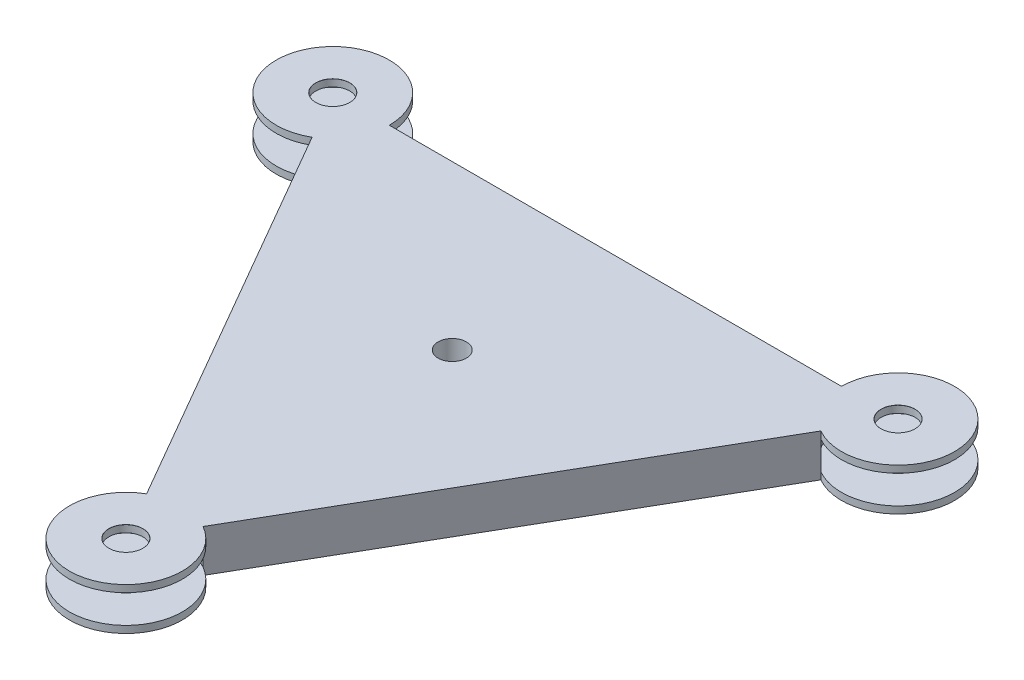
SolidWorks part; units mm, degrees
ref_plane "Plan de face" through (0, 0, 0) normal (0, 0, 1) x (1, 0, 0)
ref_plane "Plan de dessus" through (0, 0, 0) normal (0, 1, 0) x (1, 0, 0)
ref_plane "Plan de droite" through (0, 0, 0) normal (1, 0, 0) x (0, 0, -1)
sketch "Esquisse1" plane through (0, 0, 0) normal (0, 1, 0) x (1, 0, 0)
  line L3 (50, -28.8675) -> (-100, 57.735) construction
  line L6 (-50, -28.8675) -> (100, 57.735) construction
  line L16 (100, 57.735) -> (0, -115.4701)
  line L17 (0, -115.4701) -> (-100, 57.735)
  line L19 (-100, 57.735) -> (100, 57.735)
  circle A6 centre (0, 0) radius 5
  circle A7 centre (100, 57.735) radius 20
  circle A9 centre (0, -115.4701) radius 20
  circle A10 centre (-100, 57.735) radius 20
  point P11 (0, 0)
  point P12 (5.3523, 54.348)
  point P36 (0, 50)
  point P38 (0, 50)
  point P40 (0, 50)
  point P41 (0, 50)
  dimension "D2" = 5.3523
  dimension "D3" = 200
  dimension "D5" = 40
  dimension "D1" = 200
  dimension "D6" = 40
  dimension "D8" = 10
  dimension "D7" = 40
  dimension "D4" = 200
extrude "Boss.-Extru.1" add sketch "Esquisse1" along normal mid plane 15 contours A10 L17 A9 L16 A7 L19 A6 | L19 A10 L17 | L16 A7 L19 | L19 A7 L16 | L17 A10 L19 | L17 A9 L16 | L16 A9 L17 region at (102.2053, 0, -59.0083) region at (88.9734, 0, -51.3688) region at (47.9378, 0, 27.6769) region at (0, 0, 118.0165) region at (0, 0, 102.7377) region at (-88.9734, 0, -51.3688) region at (-102.2053, 0, -59.0083)
sketch "Esquisse7" plane through (0, 0, 0) normal (0, 1, 0) x (1, 0, 0)
  arc A0 (-10, -98.1495) -> (10, -98.1495) centre (0, -115.4701) ccw construction
  circle A2 centre (0, -115.4701) radius 20
  arc A4 (-80, 57.735) -> (-90, 40.4145) centre (-100, 57.735) ccw construction
  arc A6 (90, 40.4145) -> (80, 57.735) centre (100, 57.735) ccw construction
  circle A7 centre (100, 57.735) radius 20
  circle A8 centre (-100, 57.735) radius 20
  point P3 (0, 0)
  point P4 (80, 55.7158)
  point P9 (-84.1658, 45.5171)
  point P10 (0, 0)
  point P11 (80, 60.0446)
  point P13 (80, 55.7947)
  point P14 (0, 0)
  point P15 (-8.1302, -98.1495)
  point P19 (-88.1015, 40.4145)
extrude "Enlèv. mat.-Extru.1" cut sketch "Esquisse7" against normal mid plane 10
sketch "Esquisse14" plane through (0, 7.5, 0) normal (0, 1, 0) x (1, 0, 0)
  arc A0 (-80, 57.735) -> (-90, 40.4145) centre (-100, 57.735) ccw construction
  arc A2 (-10, -98.1495) -> (10, -98.1495) centre (0, -115.4701) ccw construction
  arc A3 (90, 40.4145) -> (80, 57.735) centre (100, 57.735) ccw construction
  point P17 (-100, 57.735)
  point P21 (100, 57.735)
  point P24 (0, -115.4701)
sketch "Esquisse18" plane through (0, 7.5, 0) normal (0, 1, 0) x (1, 0, 0)
  point P0 (-100, 57.735)
  point P3 (100, 57.735)
  point P6 (0, -115.4701)
hole_wizard "Dégagement M102" positions "Esquisse18" profile "Esquisse17" hole size "M10" standard "ISO" end condition through all
sketch "Esquisse17" plane through (-100, 7.5, -57.735) normal (1, 0, 0) x (0, 0, 1)
  line L0 (0, 0) -> (0, 15)
  line L1 (0, 15) -> (6, 15)
  line L2 (6, 15) -> (6, 0.025)
  line L3 (6, 0.025) -> (6.025, 0)
  line L5 (6.025, 0) -> (0, 0)
  line L6 (-6, 0.025) -> (-6.025, 0) construction
  line L11 (0, -6.35) -> (0, 107.95) construction
  dimension "Diamètre du perçage jusqu'au prochain" = 12
  dimension "Profondeur du perçage jusqu'au prochain" = 15
  dimension "Diamètre du fraisage entrant" = 12.05
  dimension "Angle du fraisage entrant" = 90
